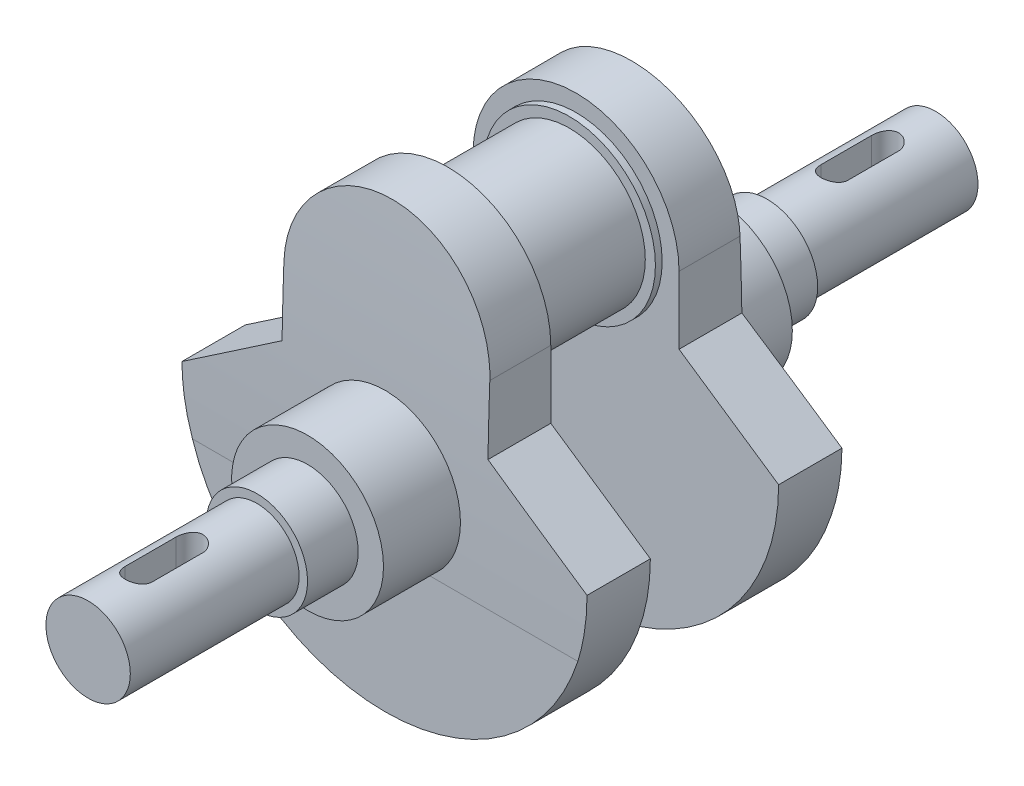
SolidWorks part; units mm, degrees
ref_plane "Front Plane" through (0, 0, 0) normal (0, 0, 1) x (1, 0, 0)
ref_plane "Top Plane" through (0, 0, 0) normal (0, 1, 0) x (1, 0, 0)
ref_plane "Right Plane" through (0, 0, 0) normal (1, 0, 0) x (0, 0, -1)
sketch "Sketch1" plane through (0, 0, 0) normal (0, 0, 1) x (1, 0, 0)
  circle A0 centre (0, 0) radius 12.5
  dimension "D1" = 25
extrude "Boss-Extrude1" add sketch "Sketch1" along normal blind 50
sketch "Sketch2" plane through (0, 0, 50) normal (0, 0, 1) x (1, 0, 0)
  circle A0 centre (0, 0) radius 15
  dimension "D1" = 30
extrude "Boss-Extrude2" add sketch "Sketch2" along normal blind 15
sketch "Sketch3" plane through (0, 0, 65) normal (0, 0, 1) x (1, 0, 0)
  circle A0 centre (0, 0) radius 22.5
  dimension "D1" = 45
extrude "Boss-Extrude3" add sketch "Sketch3" along normal blind 23
sketch "Sketch4" plane through (0, 0, 88) normal (0, 0, 1) x (1, 0, 0)
  line L0 (-57.0767, -18.5) -> (57.0767, -18.5)
  arc A0 (57.0767, -18.5) -> (-57.0767, -18.5) centre (0, 0) cw
  dimension "D1" = 60
  dimension "D2" = 18.5
extrude "Boss-Extrude4" add sketch "Sketch4" along normal blind 18.56
sketch "Sketch5" plane through (0, 0, 0) normal (1, 0, 0) x (0, 0, -1)
  line L0 (-106.56, -18.5) -> (-106.56, 70.5)
  line L1 (-106.56, 70.5) -> (-90.0672, 70.5)
  line L2 (-106.56, -18.5) -> (-88, -18.5) construction
  line L4 (-88, -18.5) -> (-106.56, -18.5)
  arc A0 (-90.0672, 70.5) -> (-88, -18.5) centre (-1122.2969, 2) cw
  dimension "D1" = 1034.5
  dimension "D2" = 89
extrude "Boss-Extrude5" add sketch "Sketch5" against normal blind 60 and the other way blind 60
sketch "Sketch7" plane through (0, 0, 88) normal (0, 0, -1) x (-1, 0, 0)
  line L0 (-60, 0) -> (-60, -18.5)
  line L1 (-60, -18.5) -> (-57.0767, -18.5)
  line L2 (60, 0) -> (60, -18.5)
  line L3 (60, -18.5) -> (57.0767, -18.5)
  arc A0 (60, 0) -> (57.0767, -18.5) centre (0, 0) cw
  arc A1 (-57.0767, -18.5) -> (-60, 0) centre (0, 0) cw
  dimension "D1" = 60
extrude "Cut-Extrude1" cut sketch "Sketch7" against normal mid plane 59.56
sketch "Sketch8" plane through (0, 0, 106.56) normal (0, 0, 1) x (1, 0, 0)
  line L0 (-60, 0) -> (-30.5, 20.0031)
  line L1 (-30.5, 20.0031) -> (-30.5, 40.0031)
  line L2 (0, 76.642) -> (0, -30.4508) construction
  line L4 (-60, 0) -> (-60, 70.5)
  line L5 (-60, 70.5) -> (60, 70.5)
  line L6 (60, 0) -> (60, 70.5)
  line L7 (30.5, 20.0031) -> (30.5, 40.0031)
  line L8 (60, 0) -> (30.5, 20.0031)
  arc A0 (-30.5, 40.0031) -> (30.5, 40.0031) centre (0, 40) cw
  line M7 (-60, 70.5) -> (-60, 0)
  line M9 (60, 0) -> (60, 70.5)
  line M10 (60, 70.5) -> (-60, 70.5)
  dimension "D1" = 30.5
  dimension "D2" = 40
  dimension "D3" = 124.14
  dimension "D4" = 20
extrude "Cut-Extrude2" cut sketch "Sketch8" against normal blind 59.56 contours A0 L7 L8 M10 M9 | L1 A0 L5 L0 M7 region at (-43.8117, 42.3607, 106.56) region at (43.8117, 42.3607, 106.56)
sketch "Sketch9" plane through (0, 0, 106.56) normal (0, 0, 1) x (1, 0, 0)
  circle A0 centre (0, 40) radius 25.5
  dimension "D1" = 51
extrude "Boss-Extrude7" add sketch "Sketch9" along normal blind 2
sketch "Sketch10" plane through (0, 0, 108.56) normal (0, 0, 1) x (1, 0, 0)
  circle A0 centre (0, 40) radius 22.5
  dimension "D1" = 45
extrude "Boss-Extrude8" add sketch "Sketch10" along normal blind 17
sketch "Sketch11" plane through (0, 0, 0) normal (0, 1, 0) x (1, 0, 0)
  line L0 (0, -15) -> (0, -30) construction
  line L1 (4, -15) -> (4, -30)
  line L2 (-4, -15) -> (-4, -30)
  line L3 (12.5, 0) -> (-12.5, 0) construction
  arc A0 (4, -15) -> (-4, -15) centre (0, -15) ccw
  arc A1 (-4, -30) -> (4, -30) centre (0, -30) ccw
  point P3 (0, -22.5)
  dimension "D1" = 4
  dimension "D2" = 15
  dimension "D3" = 15
extrude "Cut-Extrude3" cut sketch "Sketch11" along normal blind 17
mirror "Mirror1" about plane through (0, 40, 125.56) normal (0, 0, 1) of bodies 111
